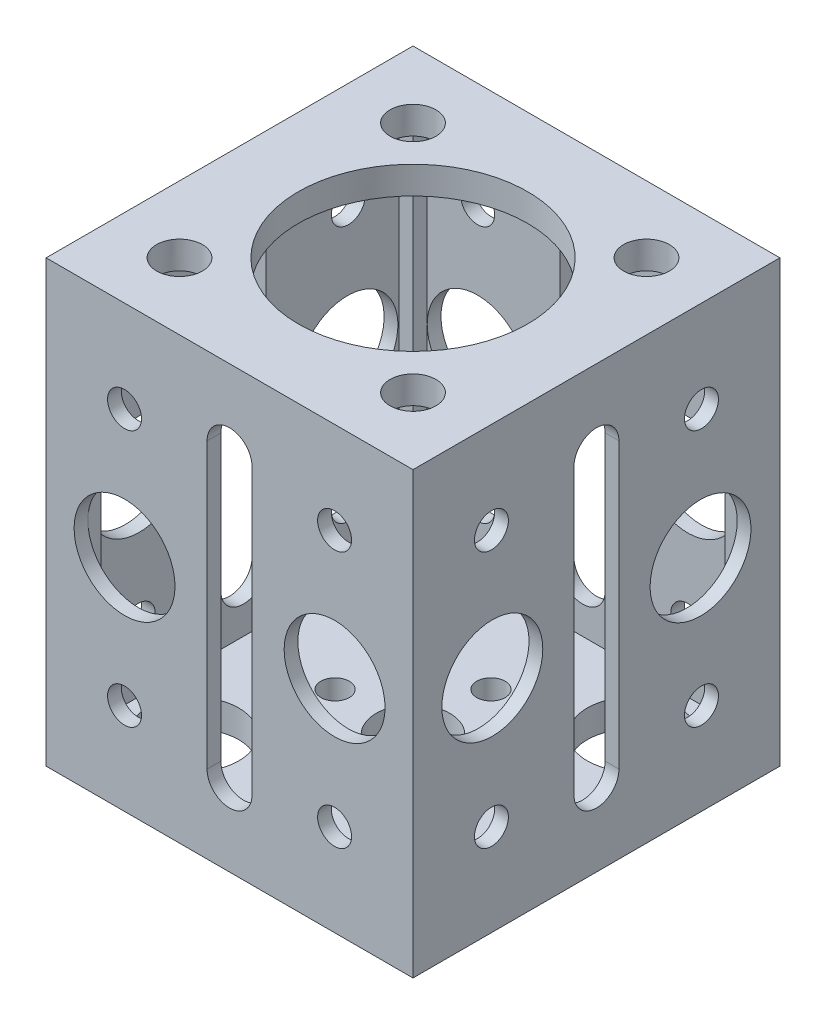
SolidWorks part; units mm, degrees
ref_plane "前视基准面" through (0, 0, 0) normal (0, 0, 1) x (1, 0, 0)
ref_plane "上视基准面" through (0, 0, 0) normal (0, 1, 0) x (1, 0, 0)
ref_plane "右视基准面" through (0, 0, 0) normal (1, 0, 0) x (0, 0, -1)
other "Configuration Table"
sketch "草图1" plane through (0, 0, 0) normal (0, 1, 0) x (1, 0, 0)
  line L0 (0, 8.5) -> (0, -8.5)
  line L1 (-20, 20) -> (20, 20)
  line L2 (-20, 20) -> (-20, -20)
  line L3 (-20, -20) -> (20, -20)
  line L4 (20, 20) -> (20, -20)
  line L5 (-20, 20) -> (20, -20) construction
  line L6 (-20, -20) -> (20, 20) construction
  line L7 (0, 0) -> (-20, 0) construction
  line L8 (-18.5, -18.5) -> (18.5, -18.5)
  line L9 (18.5, 18.5) -> (18.5, -18.5)
  line L10 (-18.5, 18.5) -> (18.5, 18.5)
  line L11 (-18.5, 18.5) -> (-18.5, -18.5)
  circle A0 centre (0, 0) radius 12.6
  circle A1 centre (0, 8.5) radius 1.55
  circle A3 centre (0, 0) radius 4
  circle A4 centre (8.5, 0) radius 1.55
  circle A5 centre (0, -8.5) radius 1.55
  circle A6 centre (-8.5, 0) radius 1.55
  point P0 (0, 0)
  point P11 (0, 0)
  point P23 (0, 0)
  dimension "D4" = 25.2
  dimension "D6" = 3.1
  dimension "D7" = 8
  dimension "D8" = 4
  dimension "D1" = 40
  dimension "D2" = 40
  dimension "D3" = 20
  dimension "D5" = 17
  dimension "D10" = 1.5
  dimension "D9" = 1.5
extrude "凸台-拉伸2" add sketch "草图1" against normal blind 3 contours L2 L3 L4 L1 | A6 | A5 | A1 | A4
extrude "切除-拉伸1" cut sketch "草图1<6>" against normal blind 1.5 contours L0 A3 | L0 A3 region at (1.6977, 0, 0) region at (-1.6977, 0, 0)
sketch "草图1<6>" plane through (0, 0, 0) normal (0, 1, 0) x (1, 0, 0) same geometry as "草图1"
sketch "草图2" plane through (0, 0, 0) normal (0, 1, 0) x (1, 0, 0)
  line L0 (-20, -20) -> (20, -20) construction
  line L1 (20, 20) -> (20, -20) construction
  line L2 (-20, 20) -> (-20, -20) construction
  line L3 (-20, 20) -> (20, 20) construction
  line L4 (-20, -20) -> (20, -20)
  line L5 (20, 20) -> (20, -20)
  line L6 (-20, 20) -> (-20, -20)
  line L7 (-20, 20) -> (20, 20)
  line L8 (0, 0) -> (38.7801, 0) construction
  line L9 (-20, 20) -> (-17, 20)
  line L10 (-20, 20) -> (-20, 17)
  line L11 (-20, 17) -> (-17, 17)
  line L12 (-17, 20) -> (-17, 17)
  line L13 (0, 0) -> (0, 17.8693) construction
  line L14 (20, -17) -> (17, -17)
  line L15 (20, 20) -> (17, 20)
  line L16 (20, 20) -> (20, 17)
  line L17 (20, 17) -> (17, 17)
  line L18 (17, 20) -> (17, 17)
  line L19 (17, -20) -> (17, -17)
  line L20 (20, -20) -> (17, -20)
  line L21 (20, -20) -> (20, -17)
  line L22 (-20, -20) -> (-20, -17)
  line L23 (-20, -20) -> (-17, -20)
  line L24 (-17, -20) -> (-17, -17)
  line L25 (-20, -17) -> (-17, -17)
  circle A0 centre (0, -8.5) radius 1.55 construction
  circle A1 centre (8.5, 0) radius 1.55 construction
  circle A2 centre (0, 8.5) radius 1.55 construction
  circle A3 centre (0, 0) radius 4 construction
  circle A4 centre (-8.5, 0) radius 1.55 construction
  circle A5 centre (0, -8.5) radius 1.55
  circle A6 centre (8.5, 0) radius 1.55
  circle A7 centre (0, 8.5) radius 1.55
  circle A8 centre (0, 0) radius 4
  circle A9 centre (-8.5, 0) radius 1.55
  point P35 (18.5, -17)
  line M9 (20, 20) -> (-20, 20)
  line M10 (-20, 20) -> (-20, -20)
  line M11 (-20, -20) -> (20, -20)
  line M12 (20, -20) -> (20, 20)
  dimension "D1" = 3
  dimension "D2" = 3
  dimension "D3" = 34
  dimension "D4" = 34
  dimension "D5" = 34
  dimension "D6" = 34
extrude "凸台-拉伸7" add sketch "草图2" along normal blind 45 contours L12 L7 L11 M10 | L18 L17 M9 M12 | L19 L4 L14 M12 | L25 L24 M10 M11 region at (-18.5, 0, 18.5) region at (18.5, 0, 18.5) region at (-18.5, 0, -18.5) region at (18.5, 0, -18.5)
sketch "草图5" plane through (-20, 0, 0) normal (-1, 0, 0) x (0, 0, 1)
  line L0 (20, -3) -> (20, 45) construction
  line L1 (-20, -3) -> (-20, 45) construction
  line L2 (20, -3) -> (20, 45)
  line L3 (-20, -3) -> (-20, 45)
  line L4 (-17, 0) -> (-17, 45)
  line L5 (-17, 45) -> (-17, 0) construction
  line L7 (-20, 45) -> (20, 45)
  line L8 (-20, 45) -> (-20, 42)
  line L9 (-20, 42) -> (20, 42)
  line L10 (20, 45) -> (20, 42)
extrude "凸台-拉伸8" add sketch "草图5" against normal blind 40 contours L8 L9 L10 L7
sketch "草图6" plane through (0, 45, 0) normal (0, 1, 0) x (1, 0, 0)
  line L0 (-20, -20) -> (0, -20)
  line L1 (0, -20) -> (0, 0)
  line L4 (20, -20) -> (20, 20)
  line L5 (20, 20) -> (-20, 20)
  line L6 (-20, 20) -> (-20, -20)
  line L7 (-20, -20) -> (20, -20)
  line L8 (20, -20) -> (20, 20)
  line L9 (20, 20) -> (-20, 20)
  line L10 (-20, 20) -> (-20, -20)
  line L11 (-20, -20) -> (20, -20)
  circle A0 centre (0, 0) radius 12.5
  dimension "D1" = 0
extrude "切除-拉伸2" cut sketch "草图6" against normal blind 4 contours A0 region at (-8.5888, 45, -8.5888)
sketch "草图7" plane through (0, -3, 0) normal (0, -1, 0) x (1, 0, 0)
  line L1 (-20, -20) -> (0, -20)
  line L2 (-20, -20) -> (-20, 0)
  line L3 (-20, 0) -> (0, 0)
  line L4 (-20, -20) -> (20, -20)
  line L5 (20, -20) -> (20, 20)
  line L6 (20, 20) -> (-20, 20)
  line L7 (-20, 20) -> (-20, -20)
  line L8 (-20, -20) -> (20, -20)
  line L9 (20, -20) -> (20, 20)
  line L10 (20, 20) -> (-20, 20)
  line L11 (-20, 20) -> (-20, -20)
  line L12 (0, -20) -> (0, 0)
  circle A0 centre (0, 0) radius 4
  dimension "D1" = 0
extrude "切除-拉伸3" cut sketch "草图7" against normal blind 4 contours L12 A0 L3 | L3 A0 L12 region at (-1.6977, -3, -1.6977) region at (0.5659, -3, 0.5659)
sketch "草图8" plane through (0, -3, 0) normal (0, -1, 0) x (1, 0, 0)
  line L0 (-20, 20) -> (0, 0) construction
  line L1 (0, 0) -> (20, 20) construction
  line L2 (-20, -20) -> (-20, 20) construction
  circle A0 centre (-12, 12) radius 5
  circle A1 centre (12, 12) radius 5
  circle A2 centre (12, -12) radius 5
  circle A3 centre (-12, -12) radius 5
  point P19 (0, 0)
  dimension "D1" = 8
  dimension "D2" = 4
extrude "切除-拉伸4" cut sketch "草图8" against normal blind 4
sketch "草图9" plane through (0, 45, 0) normal (0, 1, 0) x (1, 0, 0)
  line L0 (-20, 20) -> (0, 0) construction
  line L1 (0, 0) -> (20, 20) construction
  line L4 (20, -20) -> (20, 20)
  line L5 (20, 20) -> (-20, 20)
  line L6 (-20, 20) -> (-20, -20)
  line L7 (-20, -20) -> (20, -20)
  line L8 (20, -20) -> (20, 20)
  line L9 (20, 20) -> (-20, 20)
  line L10 (-20, 20) -> (-20, -20)
  line L11 (-20, -20) -> (20, -20)
  circle A0 centre (-12.7279, 12.7279) radius 2.5
  circle A1 centre (0, 0) radius 12.5 construction
  circle A2 centre (12.7279, 12.7279) radius 2.5
  circle A3 centre (12.7279, -12.7279) radius 2.5
  circle A4 centre (-12.7279, -12.7279) radius 2.5
  point P19 (0, 0)
  dimension "D2" = 18
  dimension "D3" = 4
  dimension "D1" = 0
extrude "切除-拉伸5" cut sketch "草图9" against normal blind 4 contours A0 | A4 | A2 | A3
sketch "草图10" plane through (0, 0, 0) normal (0, 1, 0) x (1, 0, 0)
  line L0 (20, -17) -> (17, -17) construction
  line L1 (20, 17) -> (18.5, 17)
  line L2 (20, 17) -> (20, -17)
  line L3 (20, -17) -> (18.5, -17)
  line L4 (18.5, 17) -> (18.5, -17)
  line L5 (17, -20) -> (-17, -20)
  line L6 (17, -20) -> (17, -18.5)
  line L7 (17, -18.5) -> (-17, -18.5)
  line L8 (-17, -20) -> (-17, -18.5)
  line L9 (-20, -17) -> (-20, 17)
  line L10 (-20, -17) -> (-18.5, -17)
  line L11 (-18.5, -17) -> (-18.5, 17)
  line L12 (-20, 17) -> (-18.5, 17)
  line L13 (-17, 20) -> (17, 20)
  line L14 (-17, 20) -> (-17, 18.5)
  line L15 (-17, 18.5) -> (17, 18.5)
  line L16 (17, 20) -> (17, 18.5)
  point P25 (0, 0)
  dimension "D1" = 4
extrude "凸台-拉伸10" add sketch "草图10" along normal blind 45
sketch "草图20" plane through (0, 0, 18.5) normal (0, 0, -1) x (-1, 0, 0)
  line L0 (0, 0) -> (0, 42)
  line L1 (-17, 0) -> (17, 0) construction
  line L2 (-20, -3) -> (-20, 45) construction
  line L3 (0, 0) -> (0, 3)
  line L4 (0, 3) -> (0, 5.5)
  line L5 (0, 21) -> (4.1437, 21)
  line L6 (-2.45, 36.5) -> (-2.45, 5.5)
  line L7 (2.45, 36.5) -> (2.45, 5.5)
  line L8 (-20, 45) -> (20, 45) construction
  line L9 (20, -3) -> (-20, -3) construction
  arc A1 (-2.45, 5.5) -> (2.45, 5.5) centre (0, 5.5) ccw
  arc A2 (-2.45, 36.5) -> (2.45, 36.5) centre (0, 36.5) cw
  point P10 (0, 45)
  point P13 (0, 38.95)
  point P20 (0, -3)
  point P21 (0, 3)
  dimension "D1" = 90
  dimension "D3" = 2.45
  dimension "D2" = 20
  dimension "D4" = 5.5
extrude "切除-拉伸12" cut sketch "草图20" against normal blind 4 and the other way through all contours L7 A1 L6 A2
sketch "草图24" plane through (20, 0, 0) normal (1, 0, 0) x (0, 0, -1)
  line L0 (0, -3) -> (0, 3)
  line L1 (0, 21) -> (-20, 21) construction
  line L2 (20, -3) -> (-20, -3) construction
  line L3 (0, 3) -> (0, 5.5)
  line L4 (0, -3) -> (0, 0)
  line L5 (0, 0) -> (0, 42)
  line L6 (0, 21) -> (5.4047, 21)
  line L7 (-2.45, 36.5) -> (-2.45, 5.5)
  line L8 (2.45, 5.5) -> (2.45, 36.5)
  line L9 (-20, 45) -> (20, 45) construction
  line L12 (-11.35, -3) -> (-11.35, 45) construction
  line L13 (-11.35, 21) -> (-11.35, 49) construction
  line L16 (20, -3) -> (20, 45)
  line L17 (20, 45) -> (-20, 45)
  line L18 (-20, 45) -> (-20, -3)
  line L19 (-20, -3) -> (20, -3)
  line L20 (20, -3) -> (20, 45)
  line L21 (20, 45) -> (-20, 45)
  line L22 (-20, 45) -> (-20, -3)
  line L23 (-20, -3) -> (20, -3)
  arc A0 (-2.45, 5.5) -> (2.45, 5.5) centre (0, 5.5) ccw
  arc A1 (-2.45, 36.5) -> (2.45, 36.5) centre (0, 36.5) cw
  circle A2 centre (-11.45, 35) radius 1.85
  circle A3 centre (-11.45, 7) radius 1.85
  circle A4 centre (11.45, 7) radius 1.85
  circle A5 centre (11.45, 35) radius 1.85
  circle A6 centre (-11.35, 21) radius 5.5
  circle A7 centre (11.35, 21) radius 5.5
  point P7 (0, 38.95)
  point P13 (0, 45)
  point P18 (0, 3.05)
  point P37 (-11.45, 35)
  dimension "D1" = 3
  dimension "D3" = 9
  dimension "D4" = 3.7
  dimension "D6" = 10
  dimension "D7" = 8.65
  dimension "D8" = 2.45
  dimension "D2" = 8.5
  dimension "D5" = 0
extrude "切除-拉伸13" cut sketch "草图24" along normal blind 4 and the other way through all contours L7 A0 L8 A1
extrude "切除-拉伸15" cut sketch "草图24<5>" along normal blind 10 and the other way through all contours A2 | A5 | A6 | A7 | A3 | A4
sketch "草图24<5>" plane through (20, 0, 0) normal (1, 0, 0) x (0, 0, -1) same geometry as "草图24"
sketch "草图25" plane through (0, 0, -20) normal (0, 0, -1) x (-1, 0, 0)
  line L0 (-11.45, -3) -> (-11.45, 45) construction
  line L1 (-2.45, 36.5) -> (-2.45, 5.5) construction
  line L2 (-11.45, 21) -> (-31.2071, 21) construction
  line L3 (-11.45, 45) -> (-11.45, 35) construction
  line L4 (20, -3) -> (20, 45)
  line L5 (20, 45) -> (-20, 45)
  line L6 (-20, 45) -> (-20, -3)
  line L7 (-20, -3) -> (20, -3)
  line L8 (20, -3) -> (20, 45)
  line L9 (20, 45) -> (-20, 45)
  line L10 (-20, 45) -> (-20, -3)
  line L11 (-20, -3) -> (20, -3)
  line L12 (0, 0) -> (0, 45) construction
  line L13 (-2.45, 36.5) -> (-2.45, 5.5)
  circle A0 centre (-11.45, 21) radius 5.5
  circle A1 centre (-11.45, 35) radius 1.85
  circle A2 centre (11.45, 35) radius 1.85
  circle A3 centre (11.45, 7) radius 1.85
  circle A4 centre (-11.45, 7) radius 1.85
  circle A5 centre (11.45, 21) radius 5.5
  dimension "D3" = 10
  dimension "D4" = 11
  dimension "D2" = 9
  dimension "D1" = 0
extrude "切除-拉伸16" cut sketch "草图25" along normal blind 10 and the other way through all contours A0 | A5 | A1 | A4 | A3 | A2 region at (11.45, 21, -20) region at (-11.45, 21, -20)
sketch "草图26" plane through (0, 0, -20) normal (0, 0, -1) x (-1, 0, 0)
